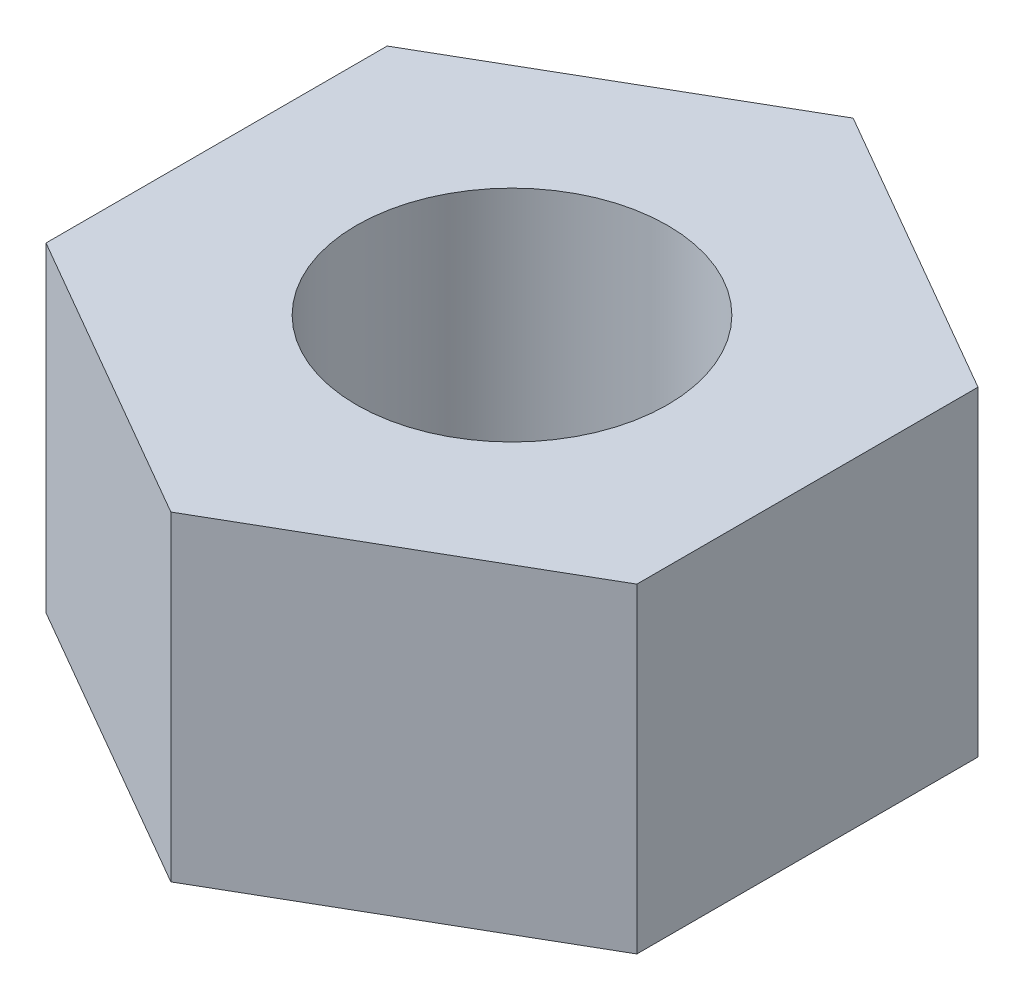
SolidWorks part; units mm, degrees
ref_plane "Front Plane" through (0, 0, 0) normal (0, 0, 1) x (1, 0, 0)
ref_plane "Top Plane" through (0, 0, 0) normal (0, 1, 0) x (1, 0, 0)
ref_plane "Right Plane" through (0, 0, 0) normal (1, 0, 0) x (0, 0, -1)
sketch "Sketch1" plane through (0, 0, 0) normal (0, 1, 0) x (1, 0, 0)
  line L1 (0, -3.2909) -> (2.85, -1.6454)
  line L2 (2.85, -1.6454) -> (2.85, 1.6454)
  line L3 (2.85, 1.6454) -> (0, 3.2909)
  line L4 (0, 3.2909) -> (-2.85, 1.6454)
  line L5 (-2.85, 1.6454) -> (-2.85, -1.6454)
  line L6 (-2.85, -1.6454) -> (0, -3.2909)
  circle A0 centre (0, 0) radius 2.85 construction
  circle A1 centre (0, 0) radius 1.5
  dimension "D2" = 3
  dimension "D1" = 5.7
extrude "Boss-Extrude1" add sketch "Sketch1" along normal blind 3.09
